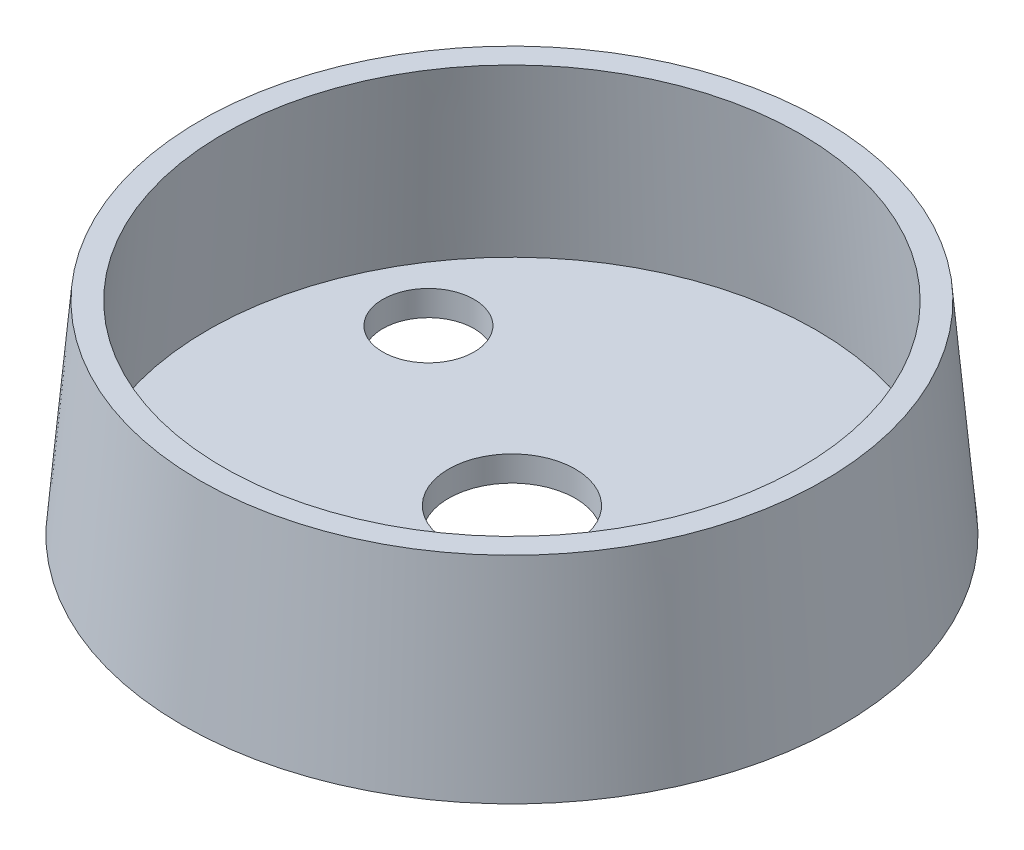
SolidWorks part; units mm, degrees
ref_plane "Front Plane" through (0, 0, 0) normal (0, 0, 1) x (1, 0, 0)
ref_plane "Top Plane" through (0, 0, 0) normal (0, 1, 0) x (1, 0, 0)
ref_plane "Right Plane" through (0, 0, 0) normal (1, 0, 0) x (0, 0, -1)
sketch "Sketch1" plane through (0, 0, 0) normal (0, 1, 0) x (1, 0, 0)
  circle A1 centre (0, 0) radius 65
  dimension "D2" = 130
extrude "Boss-Extrude1" add sketch "Sketch1" along normal blind 40 draft 5
sketch "Sketch2" plane through (0, 0, 0) normal (0, -1, 0) x (1, 0, 0)
  circle A0 centre (0, 0) radius 60
  dimension "D1" = 120
extrude "Cut-Extrude1" cut sketch "Sketch2" against normal through all draft 5 from offset 5 offset against normal yes
sketch "Sketch3" plane through (0, 0, 0) normal (0, -1, 0) x (1, 0, 0)
  circle A0 centre (0, 0) radius 12.5
  dimension "D1" = 25
extrude "Cut-Extrude2" cut sketch "Sketch3" against normal blind 21
sketch "Sketch4" plane through (0, 0, 0) normal (0, -1, 0) x (1, 0, 0)
  line L0 (0, 0) -> (0, 71.8524) construction
  line L1 (0, 0) -> (54.9556, -31.7286)
  line L2 (0, 0) -> (-52.5034, -30.3129) construction
  dimension "D1" = 120
  dimension "D2" = 120
  dimension "D3" = 120
sketch "Sketch5" plane through (0, 0, 0) normal (0, -1, 0) x (1, 0, 0)
  line L0 (-38.9711, -22.5) -> (38.9711, -22.5)
  line L1 (0, 0) -> (-52.5034, -30.3129) construction
  line L2 (0, 0) -> (54.9556, -31.7286) construction
  line L3 (38.9711, -22.5) -> (0, 45)
  line L4 (0, 0) -> (0, 71.8524) construction
  line L5 (0, 45) -> (-38.9711, -22.5)
  dimension "D1" = 45
  dimension "D2" = 45
  dimension "D3" = 45
sketch "Sketch6" plane through (0, 0, 0) normal (0, -1, 0) x (1, 0, 0)
  circle A0 centre (0, 45) radius 9
  circle A1 centre (-38.9711, -22.5) radius 9
  circle A2 centre (38.9711, -22.5) radius 9
  dimension "D1" = 18
  dimension "D2" = 18
  dimension "D3" = 18
  dimension "D4" = 18
extrude "Cut-Extrude3" cut sketch "Sketch6" against normal blind 21
